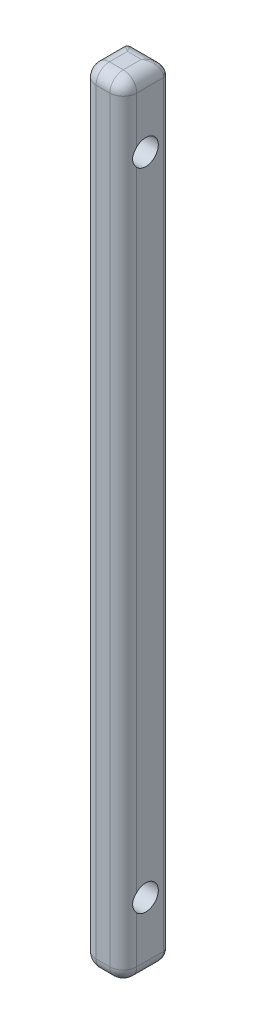
SolidWorks part; units mm, degrees
material "ABS"
ref_plane "Front Plane" through (0, 0, 0) normal (0, 0, 1) x (1, 0, 0)
ref_plane "Top Plane" through (0, 0, 0) normal (0, 1, 0) x (1, 0, 0)
ref_plane "Right Plane" through (0, 0, 0) normal (1, 0, 0) x (0, 0, -1)
sketch "Sketch1" plane through (0, 0, 0) normal (0, 0, 1) x (1, 0, 0)
  line L1 (-50.5079, 55.499) -> (-50.5079, -55.499)
  line L2 (-50.8889, 55.88) -> (-44.3611, 55.88) construction
  line L3 (-50.8889, 55.88) -> (-50.8889, -55.88) construction
  line L4 (-50.8889, -55.88) -> (-44.3611, -55.88) construction
  line L6 (-44.3611, 55.88) -> (-44.3611, -55.88) construction
  line L7 (-50.5079, -55.499) -> (-44.7421, -55.499)
  line L8 (-44.7421, 55.499) -> (-44.7421, -55.499)
  line L9 (-50.5079, 55.499) -> (-44.7421, 55.499)
  dimension "D1" = 0.381
extrude "Boss-Extrude1" add sketch "Sketch1" along normal up to surface (6.35 mm away) contours L9 L1 L7 L8
hole_wizard "#28 (0.1405) Diameter Hole1" positions "Sketch2" profile "Sketch3" hole size "#28" standard "ANSI Inch" end condition through all
sketch "Sketch2" plane through (-44.7421, 0, -6.35) normal (1, 0, 0) x (0, 1, 0)
  point P0 (45.72, 9.525)
sketch "Sketch3" plane through (-44.7421, 45.72, 3.175) normal (0, 1, 0) x (0, 0, -1)
  line L0 (0, 0) -> (0, 5.7658)
  line L1 (0, 5.7658) -> (1.7843, 5.7658)
  line L2 (1.7843, 5.7658) -> (1.7843, 0)
  line L3 (1.7843, 0) -> (0, 0)
  line L4 (0, -6.35) -> (0, 107.95) construction
  dimension "Thru Hole Dia." = 3.5687
  dimension "Thru Hole Depth" = 5.7658
mirror "Mirror1" about plane through (0, 0, 0) normal (0, 1, 0) of "#28 (0.1405) Diameter Hole1"
fillet "Fillet2" radius 1.905 10 edges at (-47.625, 55.499, 0) (-47.625, -55.499, 0) (-44.7421, 55.499, 3.175) (-44.7421, -55.499, 3.175) (-50.5079, -55.499, 3.175) (-50.5079, 55.499, 3.175) (-47.625, -55.499, 6.35) (-50.5079, 0, 6.35) (-47.625, 55.499, 6.35) (-44.7421, 0, 6.35)
fillet "Fillet3" radius 0.635 6 edges at (-45.3001, 54.941, 0.558) (-45.3001, -54.941, 0.558) (-49.9499, 54.941, 0.558) (-49.9499, -54.941, 0.558) (-44.7421, 0, 0) (-50.5079, 0, 0)
